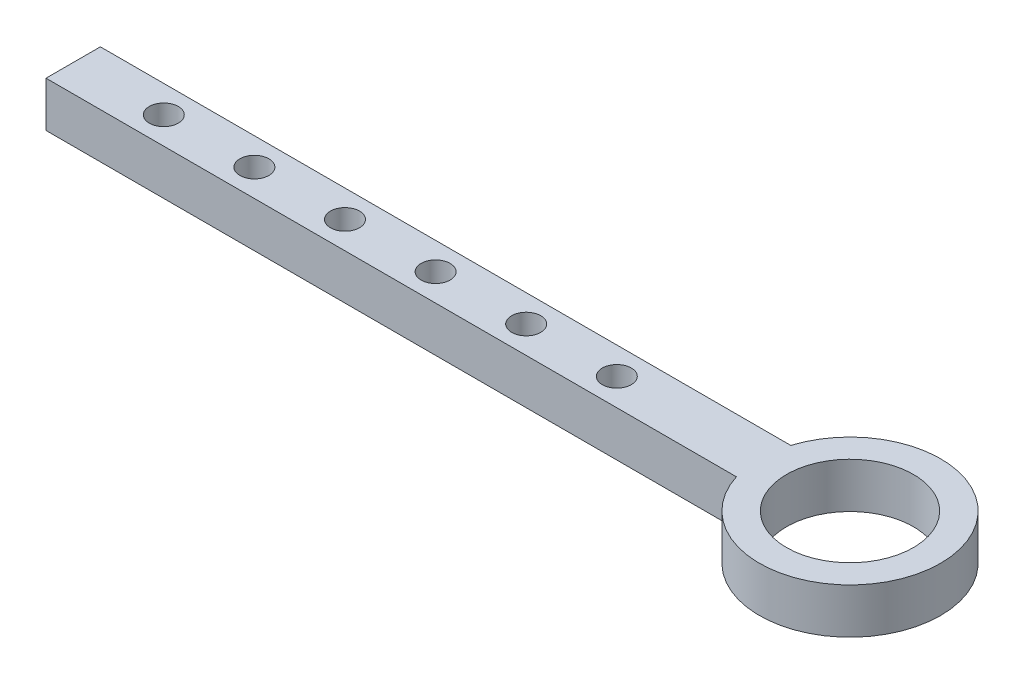
SolidWorks part; units mm, degrees
ref_plane "Front" through (0, 0, 0) normal (0, 0, 1) x (1, 0, 0)
ref_plane "Top" through (0, 0, 0) normal (0, 1, 0) x (1, 0, 0)
ref_plane "Right" through (0, 0, 0) normal (1, 0, 0) x (0, 0, -1)
sketch "Sketch1" plane through (0, 0, 0) normal (0, 1, 0) x (1, 0, 0)
  line L0 (0, 3) -> (76.2, 3)
  line L1 (0, 0) -> (76.2, 0)
  line L2 (0, 0) -> (0, 6)
  line L3 (0, 6) -> (76.2, 6)
  line L4 (76.2, 0) -> (76.2, 6)
  circle A0 centre (85.7394, 3) radius 10
  circle A1 centre (85.7394, 3) radius 7
  circle A2 centre (10, 3) radius 1.6
  circle A3 centre (20, 3) radius 1.6
  circle A4 centre (30, 3) radius 1.6
  circle A5 centre (40, 3) radius 1.6
  circle A6 centre (50, 3) radius 1.6
  circle A7 centre (60, 3) radius 1.6
  dimension "D3" = 10
  dimension "D1" = 6
  dimension "D2" = 76.2
  dimension "D4" = 6
extrude "Boss-Extrude1" add sketch "Sketch1" along normal blind 5 contours L4 A0 A1 | L4 A0 L0 | L0 A0 L4 | A7 L0 A6 A5 A4 A3 A2 L2 L1 A0 | A7 L0 A0 L3 L2 A2 A3 A4 A5 A6 region at (38.2951, 0, -4.599) region at (38.2951, 0, -1.401) region at (76.0154, 0, -1.8715) region at (76.4796, 0, -1.5) region at (76.0154, 0, -4.1285)
